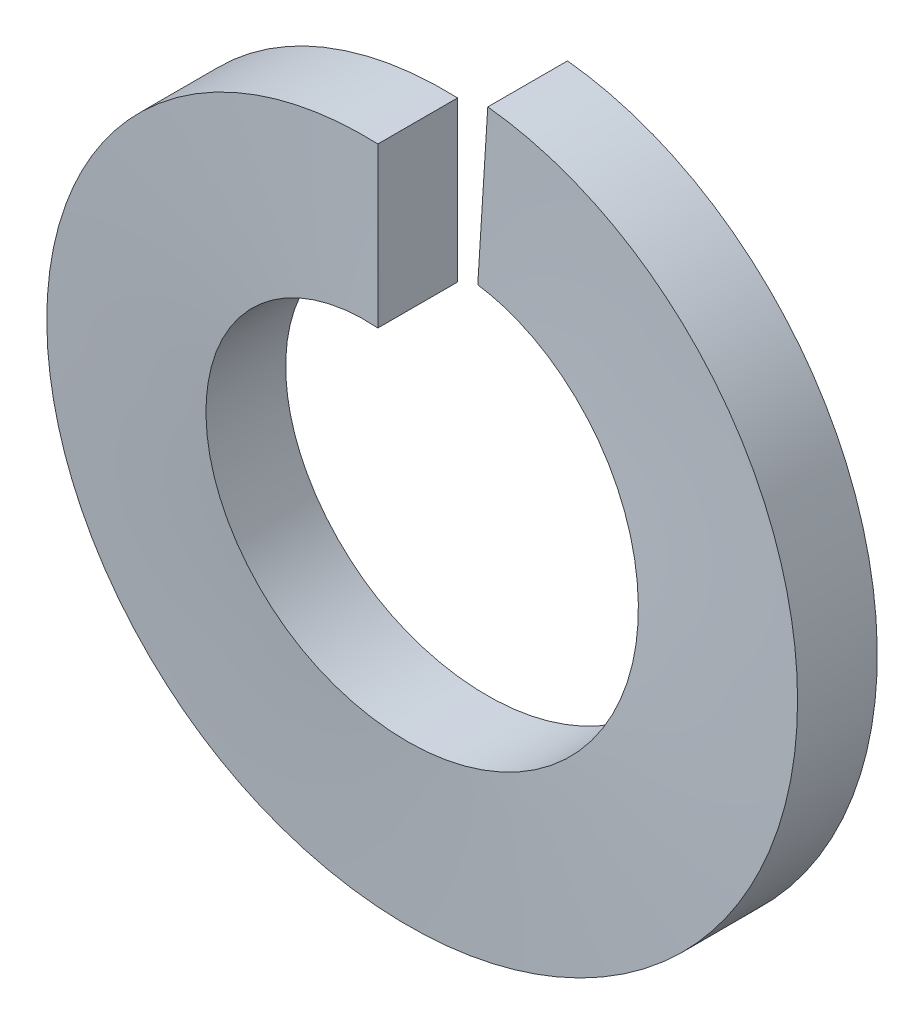
SolidWorks part; units mm, degrees
ref_plane "Front Plane" through (0, 0, 0) normal (0, 0, 1) x (1, 0, 0)
ref_plane "Top Plane" through (0, 0, 0) normal (0, 1, 0) x (1, 0, 0)
ref_plane "Right Plane" through (0, 0, 0) normal (1, 0, 0) x (0, 0, -1)
sketch "Spiral Sketch" plane through (0, 0, 0) normal (0, 0, 1) x (1, 0, 0)
  line L0 (0, 3.1) -> (0, 1.7) construction
  circle A0 centre (0, 0) radius 3.1
  circle A1 centre (0, 0) radius 1.7 construction
  dimension "ID" = 3.4
  dimension "OD" = 6.2
curve "Spiral" pitch 0.7778 height 0.77 radius 3.1 left hand yes centre (0, 0, 0) axis (0, 0, -1) start towards (0, 1, 0) parameters "HT"=0.77
sketch "Profile Sketch" plane through (0, 0, 0) normal (1, 0, 0) x (0, 0, -1)
  line L1 (0, 3.1) -> (-0.7, 3.1)
  line L2 (0, 3.1) -> (0, 1.7)
  line L3 (0, 1.7) -> (-0.7, 1.7)
  line L4 (-0.7, 3.1) -> (-0.7, 1.7)
  dimension "Thickness" = 0.7
sweep "Profile Sweep" add profiles "Profile Sketch" path "Spiral"
ref_axis "Center Axis 1" through (0, 0, -2.2957) along (0, 0, 1)
ref_plane "Contact Plane 1" through (0, 0, 0.7) normal (0, 0, 1) x (1, 0, 0)
ref_plane "Contact Plane 2" through (0, 0, -0.7703) normal (0, 0, 1) x (1, 0, 0)
equation "\"HT@Spiral\" = \"Thickness@Profile Sketch\" * 1.1"
